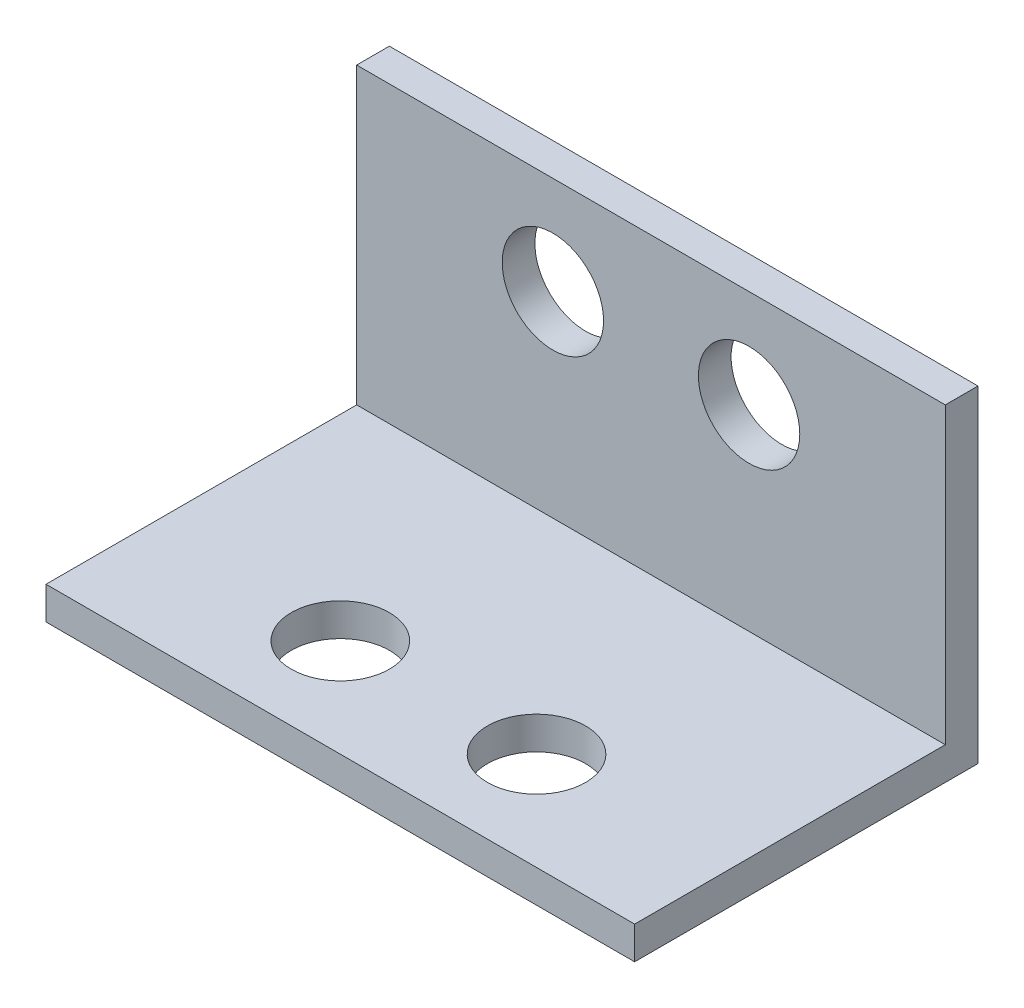
SolidWorks part; units mm, degrees
other "Markup1"
sketch "Sketch3" plane through (0, 3, -10.5) normal (0, 1, 0) x (1, 0, 0)
ref_plane "Front Plane" through (0, 0, 0) normal (0, 0, 1) x (1, 0, 0)
ref_plane "Top Plane" through (0, 0, 0) normal (0, 1, 0) x (1, 0, 0)
ref_plane "Right Plane" through (0, 0, 0) normal (1, 0, 0) x (0, 0, -1)
sketch "Sketch1" plane through (0, 0, 0) normal (0, 1, 0) x (1, 0, 0)
  line L1 (0, 0) -> (18, 0)
  line L2 (0, 0) -> (0, 10.5)
  line L3 (0, 10.5) -> (18, 10.5)
  line L4 (18, 0) -> (18, 10.5)
  circle A0 centre (6, 3) radius 1.5
  circle A1 centre (12, 3) radius 1.5
  dimension "D2" = 3
  dimension "D3" = 6
  dimension "D4" = 3
  dimension "D5" = 3
  dimension "D6" = 6
  dimension "D7" = 3
  dimension "D1" = 10.5
  dimension "18" = 18
extrude "Boss-Extrude1" add sketch "Sketch1" along normal blind 1
sketch "Sketch2" plane through (0, 1, 0) normal (0, 1, 0) x (1, 0, 0)
  line L0 (18, 0) -> (18, 10.5) construction
  line L1 (0, 10.5) -> (18, 10.5)
  line L2 (0, 10.5) -> (0, 9.5)
  line L3 (0, 9.5) -> (18, 9.5)
  line L4 (18, 10.5) -> (18, 9.5)
  dimension "D1" = 1
extrude "Boss-Extrude2" add sketch "Sketch2" along normal blind 9
sketch "Sketch4" plane through (0, 0, -9.5) normal (0, 0, 1) x (1, 0, 0)
  line L0 (0, 10) -> (0, 1) construction
  line L1 (0, 10) -> (18, 10) construction
  circle A0 centre (6, 7) radius 1.55
  circle A1 centre (12, 7) radius 1.55
  dimension "D1" = 3.1
  dimension "D2" = 3.1
  dimension "D3" = 6
  dimension "D4" = 6
  dimension "D5" = 3
  dimension "D6" = 3
extrude "Cut-Extrude1" cut sketch "Sketch4" against normal through all
